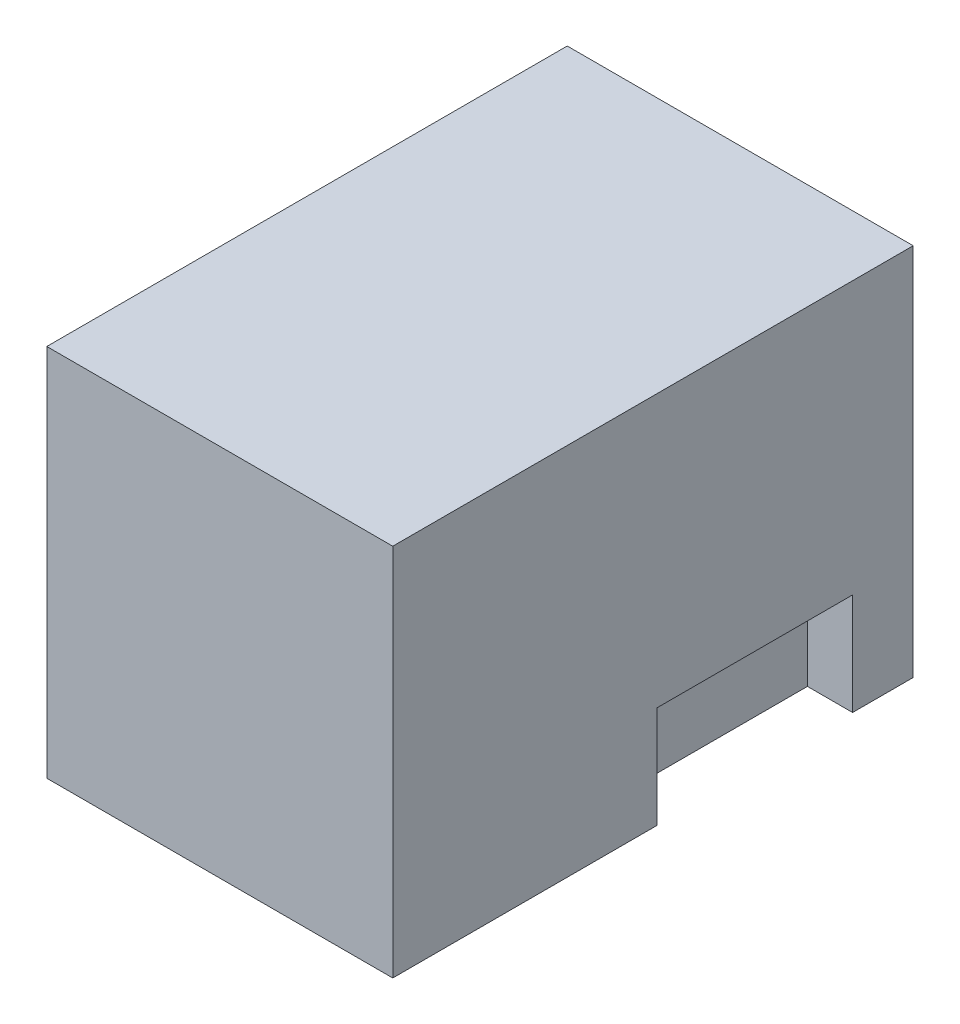
SolidWorks part; units mm, degrees
ref_plane "Front Plane" through (0, 0, 0) normal (0, 0, 1) x (1, 0, 0)
ref_plane "Top Plane" through (0, 0, 0) normal (0, 1, 0) x (1, 0, 0)
ref_plane "Right Plane" through (0, 0, 0) normal (1, 0, 0) x (0, 0, -1)
sketch "Sketch1" plane through (0, 0, 0) normal (0, 1, 0) x (1, 0, 0)
  line L1 (0, 0) -> (217.5, 0)
  line L2 (0, 0) -> (0, 327.2)
  line L3 (0, 327.2) -> (217.5, 327.2)
  line L4 (217.5, 0) -> (217.5, 327.2)
  dimension "D1" = 217.5
  dimension "D2" = 327.2
extrude "Boss-Extrude1" add sketch "Sketch1" along normal blind 235.1
shell "Shell1" thickness 2 removed face at (108.75, 117.55, -327.2)
sketch "Left_wheel_space_sketch" plane through (217.5, 0, 0) normal (1, 0, 0) x (0, 0, -1)
  line L0 (327.2, 0) -> (227.6, 0) construction
  line L1 (0, 0) -> (327.2, 0) construction
  line L3 (291.1, 0) -> (164.1, 0)
  line L4 (291.1, 0) -> (291.1, 66.04)
  line L5 (291.1, 66.04) -> (164.1, 66.04)
  line L6 (164.1, 0) -> (164.1, 66.04)
  circle A0 centre (227.6, 0) radius 50.8 construction
  point P11 (227.6, 0)
  dimension "D3" = 99.6
  dimension "D4" = 101.6
  dimension "D1" = 127
  dimension "D2" = 66.04
sketch "Right_wheel_space_sketch" plane through (0, 0, 0) normal (-1, 0, 0) x (0, 0, 1)
  line L4 (-291.1, 0) -> (-164.1, 0)
  line L5 (-164.1, 0) -> (-164.1, 66.04)
  line L6 (-164.1, 66.04) -> (-291.1, 66.04)
  line L7 (-291.1, 66.04) -> (-291.1, 0)
  line L8 (-291.1, 0) -> (-164.1, 0)
  line L9 (-164.1, 0) -> (-164.1, 66.04)
  line L10 (-164.1, 66.04) -> (-291.1, 66.04)
  line L11 (-291.1, 66.04) -> (-291.1, 0)
  dimension "D1" = 0
extrude "Left_wheel_space" add sketch "Left_wheel_space_sketch" against normal blind 30
extrude "Right_wheel_space" add sketch "Right_wheel_space_sketch" against normal blind 30
sketch "Sketch9" plane through (217.5, 0, 0) normal (1, 0, 0) x (0, 0, -1)
  line L0 (289.1, 0) -> (289.1, 64.04)
  line L1 (289.1, 64.04) -> (166.1, 64.04)
  line L2 (166.1, 64.04) -> (166.1, 0)
  line L4 (164.1, 0) -> (291.1, 0)
  line L5 (164.1, 66.04) -> (164.1, 0)
  line L6 (291.1, 66.04) -> (164.1, 66.04)
  line L7 (291.1, 0) -> (291.1, 66.04)
  line L8 (166.1, 0) -> (289.1, 0)
  line L12 (166.1, 2) -> (289.1, 2) construction
  line L13 (164.1, 66.04) -> (164.1, 0) construction
  line L14 (291.1, 66.04) -> (164.1, 66.04) construction
  line L15 (291.1, 0) -> (291.1, 66.04) construction
  line L17 (166.1, 64.04) -> (166.1, 2) construction
  line L18 (289.1, 2) -> (289.1, 64.04) construction
  line L19 (164.1, 0) -> (291.1, 0) construction
  point P9 (0, 0)
  dimension "D1" = 0
  dimension "D2" = 2
extrude "Left_wheel_space_cut" cut sketch "Sketch9" against normal blind 28.4
sketch "Sketch10" plane through (0, 0, 0) normal (-1, 0, 0) x (0, 0, 1)
  line L4 (-289.1, 64.04) -> (-289.1, 0)
  line L5 (-166.1, 64.04) -> (-289.1, 64.04)
  line L6 (-166.1, 0) -> (-166.1, 64.04)
  line L7 (-289.1, 0) -> (-166.1, 0)
  line L8 (-289.1, 64.04) -> (-289.1, 0)
  line L9 (-166.1, 64.04) -> (-289.1, 64.04)
  line L10 (-166.1, 0) -> (-166.1, 64.04)
  line L11 (-289.1, 0) -> (-166.1, 0)
  dimension "D1" = 0
extrude "Right_wheel_space_cut" cut sketch "Sketch10" against normal blind 28.4
